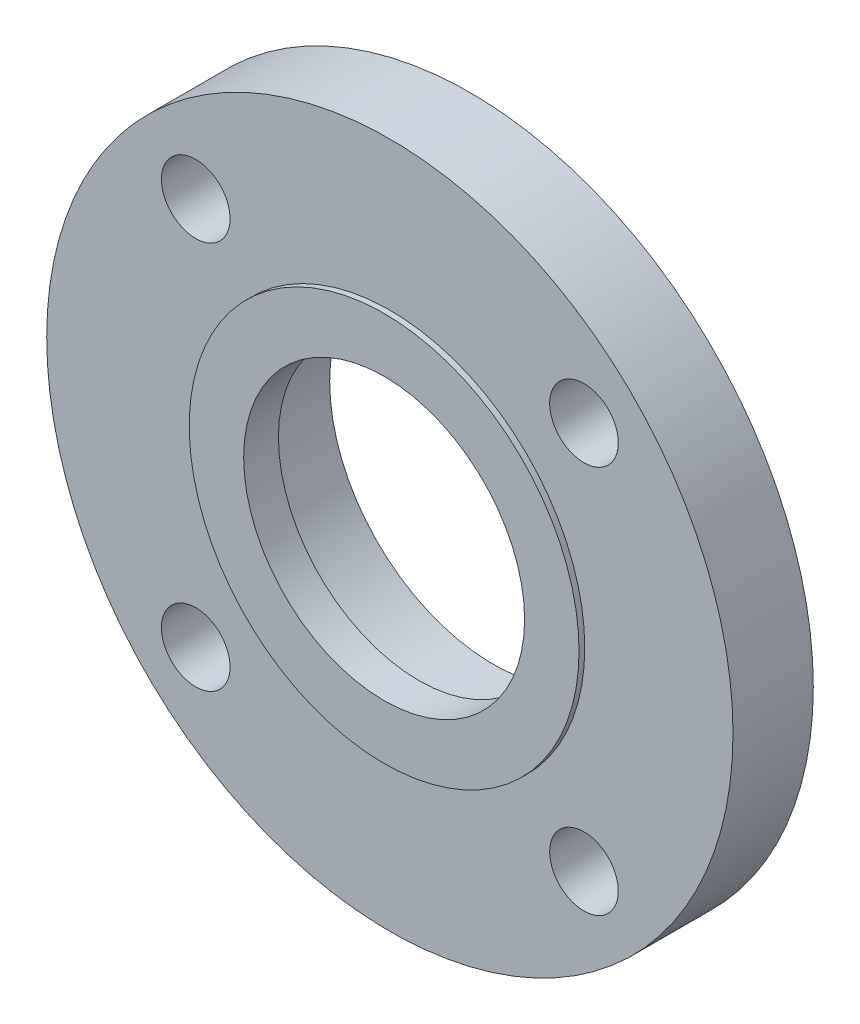
SolidWorks part; units mm, degrees
ref_plane "front" through (0, 0, 0) normal (0, 0, 1) x (1, 0, 0)
ref_plane "top" through (0, 0, 0) normal (0, 1, 0) x (1, 0, 0)
ref_plane "side" through (0, 0, 0) normal (1, 0, 0) x (0, 0, -1)
sketch "Hub Diameter" plane through (0, 0, 0) normal (0, 0, 1) x (1, 0, 0)
  circle A0 centre (0, 0) radius 54.102
  dimension "Diameter of Hub X" = 108.204
extrude "Hub" add sketch "Hub Diameter" against normal blind 30.226
ref_plane "Flange starting plane" through (0, 0, -1.5875) normal (0, 0, 1) x (1, 0, 0)
ref_plane "Flange end plane" through (0, 0, -23.876) normal (0, 0, 1) x (1, 0, 0)
sketch "Flange Diameter" plane through (0, 0, -1.5875) normal (0, 0, 1) x (1, 0, 0)
  circle A0 centre (0, 0) radius 95.25
  dimension "Outside Diameter of Flange O" = 190.5
extrude "Flange" add sketch "Flange Diameter" against normal up to surface (22.2885 mm away) up to plane "Flange end plane"
ref_axis "Axis of Revolution for Bore" through (0, 0, -50) along (0, 0, 1)
sketch "Bolt Diameter" plane through (0, 0, -1.5875) normal (0, 0, 1) x (1, 0, 0)
  line L0 (0, 31.297) -> (0, -28.4144) construction
  line L1 (23.6001, 23.6001) -> (-21.885, -21.885) construction
  circle A0 centre (53.8815, 53.8815) radius 9.525
  circle A1 centre (0, 0) radius 76.2 construction
  point P0 (0, 0)
  dimension "Diameter of Bolt Holes" = 19.05
  dimension "Diameter of Bolt Circle" = 152.4
  dimension "Angle" = 45
extrude "Bolt Hole" cut sketch "Bolt Diameter" against normal through all
pattern_circular "Bolt Hole Pattern" count 4 every 90 about axis through (0, 0, -50) along (0, 0, 1) of "Bolt Hole"
sketch "Socket Diameter" plane through (0, 0, 0) normal (0, 0, 1) x (1, 0, 0)
  circle A0 centre (0, 0) radius 38.989
  dimension "Socket Bore" = 77.978
extrude "Socket" cut sketch "Socket Diameter" against normal through all
sketch "Bore Diameter" plane through (0, 0, -30.226) normal (0, 0, -1) x (-1, 0, 0)
  circle A0 centre (0, 0) radius 45.339
  dimension "Bore B" = 90.678
extrude "Bore" cut sketch "Bore Diameter" against normal blind 20.574
sketch "Sketch1" plane through (0, 0, 0) normal (0, 1, 0) x (1, 0, 0)
  line L1 (38.989, 9.652) -> (-38.989, 9.652) construction
  line L2 (-54.102, 0) -> (54.102, 0) construction
  point P0 (0, 0)
  point P1 (0, 9.652)
other "CPoint1" parameters "Diameter"=76.2, "StubLength"=0
ref_axis "Axis1" through (0, 0, -19.652) along (0, 0, 1)
other "RPoint1"
ref_axis "Axis of Rotation" through (0, 0, -9.652) along (0, 0, -1)
ref_axis "Vertical" through (0, 0, -9.652) along (0, 1, 0)
equation "\"flange height@Flange starting plane\" =  ( \"Hub Length Y@Hub\" - \"Thickness of Flange C@Flange end plane\" )  / 3"
equation "\"angular position of Bolt Holes@Bolt Hole Pattern\" = 360/\"Number of Bolt Holes@Bolt Hole Pattern\""
